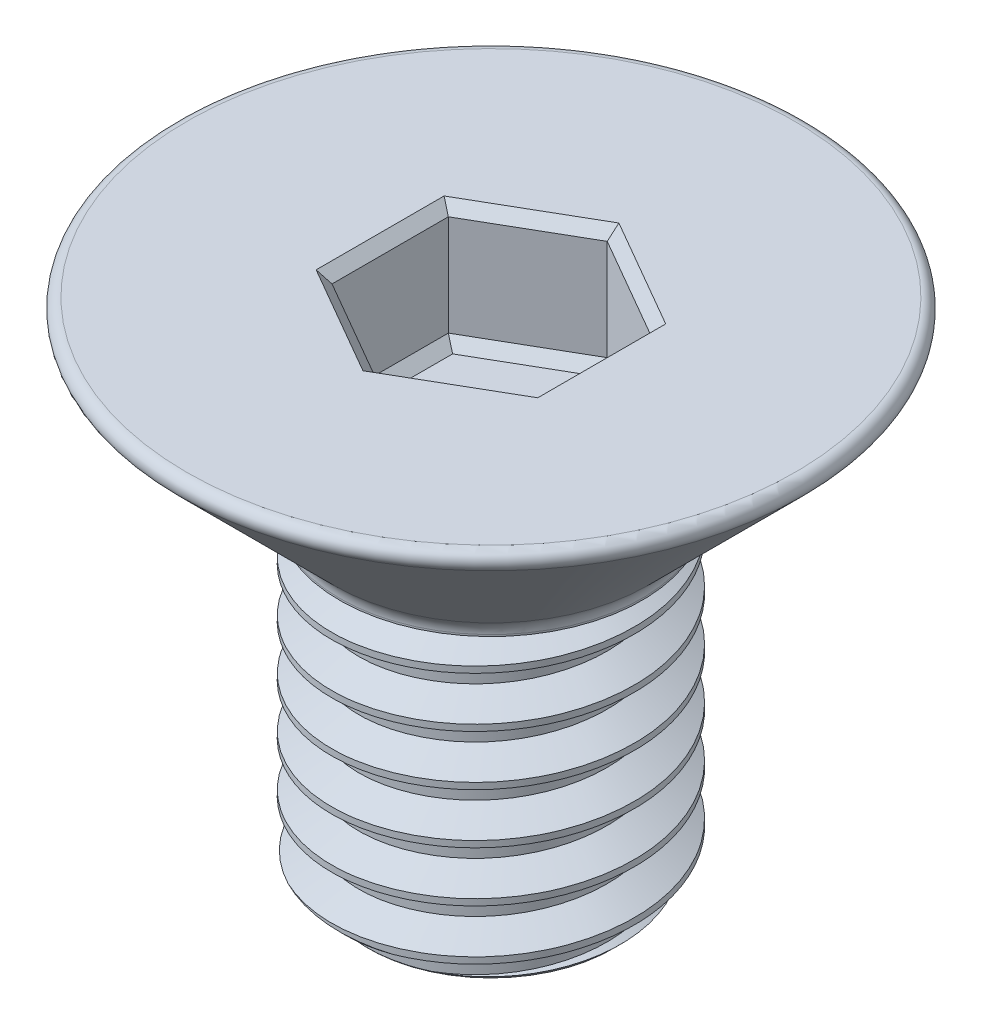
SolidWorks part; units mm, degrees
material "AISI Type A2 Tool Steel"
ref_plane "Front Plane" through (0, 0, 0) normal (0, 0, 1) x (1, 0, 0)
ref_plane "Top Plane" through (0, 0, 0) normal (0, 1, 0) x (1, 0, 0)
ref_plane "Right Plane" through (0, 0, 0) normal (1, 0, 0) x (0, 0, -1)
sketch "Sketch1" plane through (0, 0, 0) normal (0, 1, 0) x (1, 0, 0)
  circle A0 centre (0, 0) radius 1.5
  dimension "D1" = 3
extrude "Boss-Extrude1" add sketch "Sketch1" along normal blind 3.14
thread "Thread1" pitch 0.5 method cut profile "Thread Profile1" start angle 0, offset 1, length 0, pitch 0.5, diameter 3
ref_plane "Plane1" through (-1.5, 4.14, 0) normal (0, 0, 1) x (-1, 0, 0)
sketch "Thread Profile1" plane through (-1.5, 4.14, 0) normal (0, 0, 1) x (-1, 0, 0)
  line L0 (0, 0) -> (0, 0.5) construction
  line L11 (0, 0) -> (0, 0.4375)
  line L12 (0, 0.4375) -> (-0.2706, 0.2812)
  line L13 (-0.2706, 0.2812) -> (-0.2706, 0.1562)
  line L15 (-0.2706, 0.1562) -> (0, 0)
  line L17 (-0.2706, 0.2187) -> (0, 0.2187) construction
  point P2 (0, 0)
  dimension "Pitch" = 0.5
  dimension "Profile_Angle" = 60
  dimension "Profile_Land" = 0.125
  dimension "Profile_Height" = 0.2706
sketch "Sketch5" plane through (0, 3.14, 0) normal (0, 1, 0) x (1, 0, 0)
  circle A0 centre (0, 0) radius 1.5
  dimension "D1" = 3
extrude "Boss-Extrude2" add sketch "Sketch5" along normal blind 0.1
sketch "Sketch6" plane through (0, 3.24, 0) normal (0, 1, 0) x (1, 0, 0)
  circle A0 centre (0, 0) radius 1.5
  dimension "D1" = 3
extrude "Boss-Extrude3" add sketch "Sketch6" along normal blind 1.76 draft 45 draft outward yes
sketch "Sketch7" plane through (0, 0, 0) normal (0, 0, 1) x (1, 0, 0)
  line L0 (0, 0) -> (0, 0.1997) construction
  line L1 (0, 0) -> (1.51, 0) construction
  line L2 (1.51, 0) -> (1.51, 0.3)
  line L3 (1.51, 0.3) -> (1.21, 0)
  line L4 (1.21, 0) -> (1.51, 0)
  dimension "D1" = 45
  dimension "D2" = 0.3
  dimension "D3" = 1.51
revolve "Cut-Revolve1" cut sketch "Sketch7" angle 360 about L0
fillet "Fillet1" radius 0.1 1 edges at (0, 5, 3.26)
fillet "Fillet2" radius 0.2 1 edges at (0, 3.24, 1.5)
sketch "Sketch8" plane through (0, 5, 0) normal (0, 1, 0) x (1, 0, 0)
  line L1 (0, 1.1547) -> (-1, 0.5774)
  line L2 (-1, 0.5774) -> (-1, -0.5774)
  line L3 (-1, -0.5774) -> (0, -1.1547)
  line L4 (0, -1.1547) -> (1, -0.5774)
  line L5 (1, -0.5774) -> (1, 0.5774)
  line L6 (1, 0.5774) -> (0, 1.1547)
  circle A0 centre (0, 0) radius 1 construction
  dimension "D1" = 2
extrude "Cut-Extrude1" cut sketch "Sketch8" against normal blind 1.1
chamfer "Chamfer1" distance 0.1 angle 45 6 edges at (-1, 5, 0) (-0.5, 5, 0.866) (0.5, 5, 0.866) (1, 5, 0) (0.5, 5, -0.866) (-0.5, 5, -0.866)
sketch "Sketch9" plane through (0, 3.9, 0) normal (0, 1, 0) x (1, 0, 0)
  line L1 (0, 1.1547) -> (-1, 0.5774)
  line L2 (-1, 0.5774) -> (-1, -0.5774)
  line L3 (-1, -0.5774) -> (0, -1.1547)
  line L4 (0, -1.1547) -> (1, -0.5774)
  line L5 (1, -0.5774) -> (1, 0.5774)
  line L6 (1, 0.5774) -> (0, 1.1547)
  circle A0 centre (0, 0) radius 1 construction
extrude "Cut-Extrude2" cut sketch "Sketch9" against normal blind 0.1 draft 45
